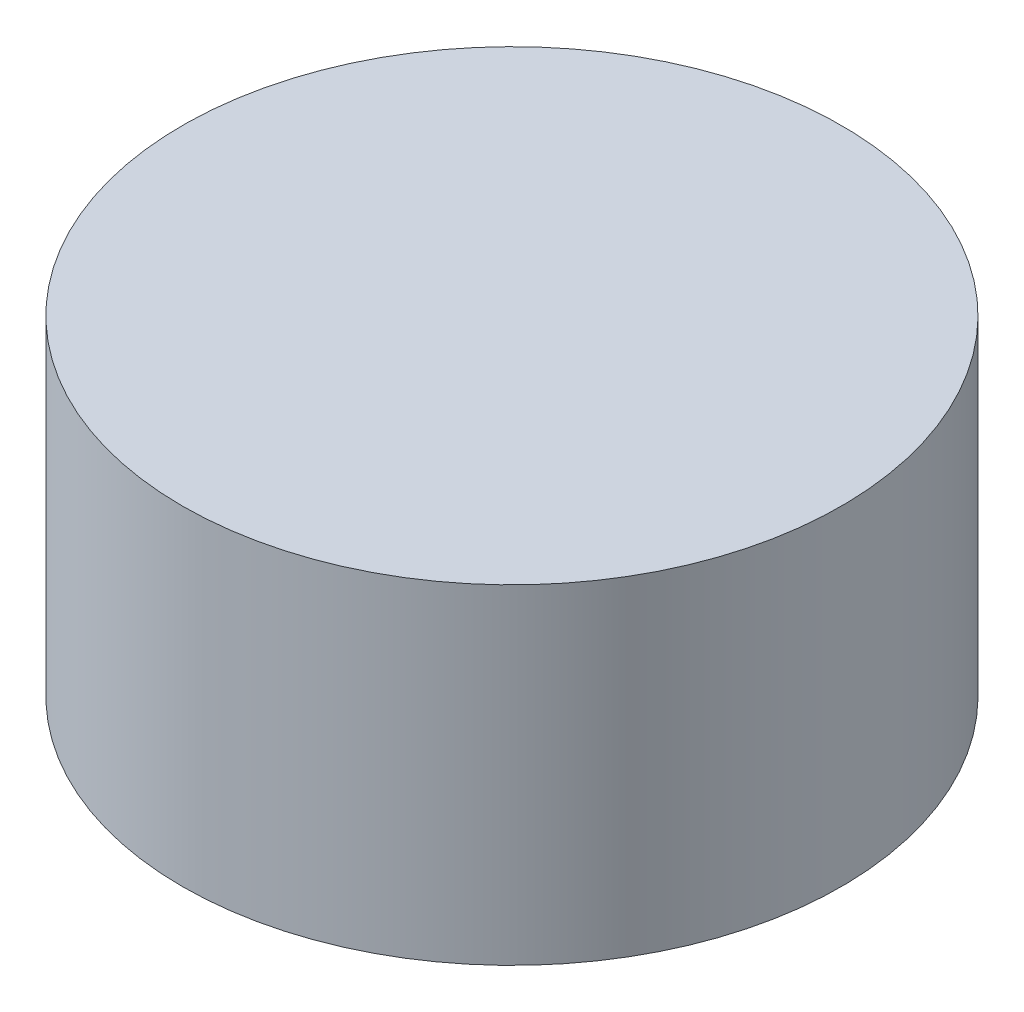
SolidWorks part; units mm, degrees
ref_plane "Front Plane" through (0, 0, 0) normal (0, 0, 1) x (1, 0, 0)
ref_plane "Top Plane" through (0, 0, 0) normal (0, 1, 0) x (1, 0, 0)
ref_plane "Right Plane" through (0, 0, 0) normal (1, 0, 0) x (0, 0, -1)
sketch "Sketch1" plane through (0, 0, 0) normal (0, 1, 0) x (1, 0, 0)
  circle A0 centre (0, 0) radius 12.7
  dimension "D1" = 25.4
extrude "Boss-Extrude1" add sketch "Sketch1" along normal blind 12.7
